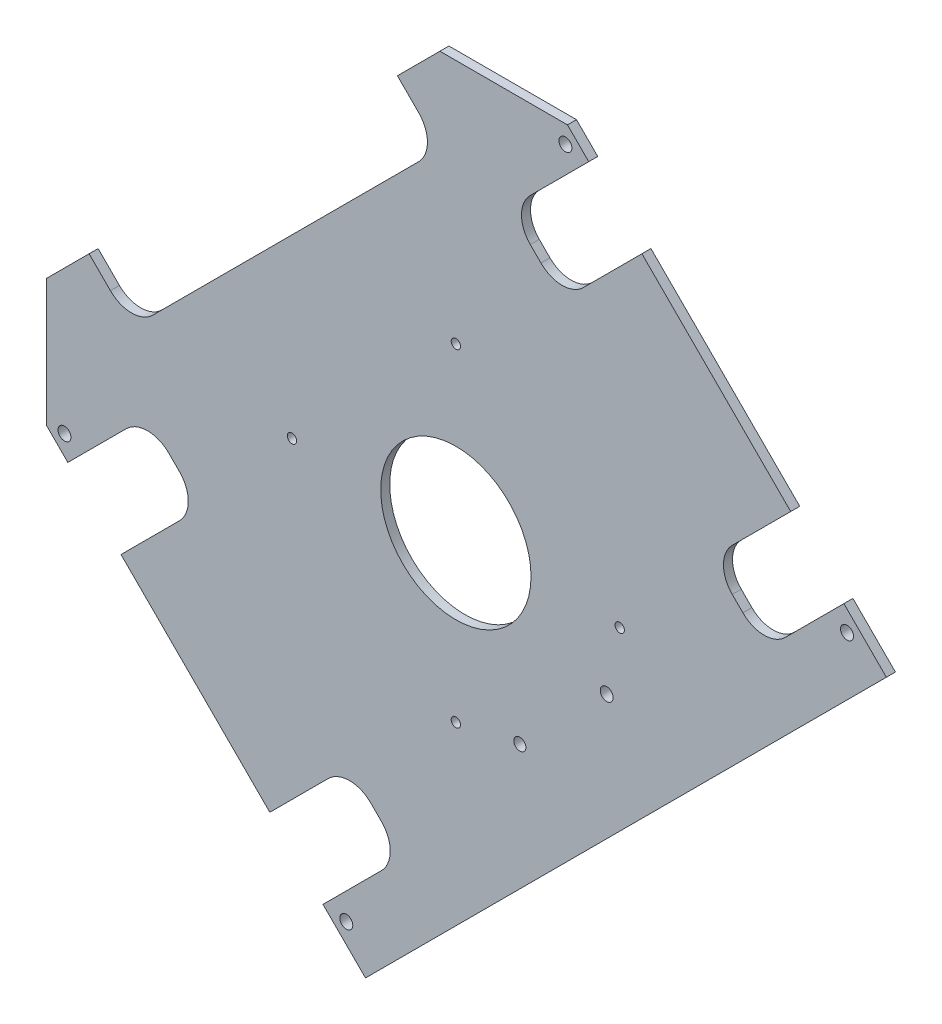
SolidWorks part; units mm, degrees
ref_plane "前视基准面" through (0, 0, 0) normal (0, 0, 1) x (1, 0, 0)
ref_plane "上视基准面" through (0, 0, 0) normal (0, 1, 0) x (1, 0, 0)
ref_plane "右视基准面" through (0, 0, 0) normal (1, 0, 0) x (0, 0, -1)
sketch "Sketch1" plane through (0, 0, 0) normal (0, 0, 1) x (1, 0, 0)
  line L16 (44.1941, 129.0469) -> (15.9098, 157.3312)
  line L17 (-110.8692, -62.3719) -> (-111.3693, -61.8718)
  line L18 (15.9098, 157.3312) -> (-19.4455, 121.9759)
  line L20 (61.1787, 112.0623) -> (111.3693, 61.8718)
  line L21 (-110.8692, -62.3719) -> (-61.8718, -111.3693)
  line L22 (143.1891, 30.052) -> (-30.052, -143.1891)
  line L23 (10.9602, -120.5617) -> (86.6206, -196.2221) construction
  line L24 (196.2221, -86.6206) -> (120.5617, -10.9602) construction
  line L25 (120.5617, -6.7176) -> (141.7749, 14.4956) construction
  line L26 (14.4956, 141.7749) -> (-6.7176, 120.5617) construction
  line L27 (61.1787, 112.0623) -> (61.8718, 111.3693)
  line L28 (44.1941, 129.0469) -> (17.6776, 102.5304)
  line L29 (61.8718, 111.3693) -> (35.3553, 84.8528)
  line L30 (17.6776, 102.5304) -> (35.3553, 84.8528)
  line L32 (111.3693, 61.8718) -> (84.8528, 35.3553)
  line L33 (129.0469, 44.1941) -> (102.5304, 17.6776)
  line L34 (84.8528, 35.3553) -> (102.5304, 17.6776)
  line L35 (56.5685, -56.5685) -> (-56.5685, 56.5685) construction
  line L36 (-35.3553, -84.8528) -> (-17.6776, -102.5304)
  line L37 (-44.1941, -129.0469) -> (-17.6776, -102.5304)
  line L38 (-61.8718, -111.3693) -> (-35.3553, -84.8528)
  line L40 (-102.5304, -17.6776) -> (-84.8528, -35.3553)
  line L41 (-111.3693, -61.8718) -> (-84.8528, -35.3553)
  line L42 (-129.0469, -44.1941) -> (-102.5304, -17.6776)
  line L44 (48.0832, 104.6517) -> (37.4766, 94.0451) construction
  line L45 (94.0451, 37.4766) -> (104.6517, 48.0832) construction
  line L46 (115.2584, 37.4766) -> (104.6517, 26.87) construction
  line L47 (102.5304, 24.7487) -> (98.9949, 28.2842) construction
  line L48 (28.2842, 98.9949) -> (24.7487, 102.5304) construction
  line L50 (-121.9759, 19.4455) -> (-107.8337, 5.3034)
  line L51 (-19.4455, 121.9759) -> (-5.3034, 107.8337)
  line L52 (-107.8337, 5.3034) -> (-5.3034, 107.8337)
  line L53 (-121.9759, 19.4455) -> (-157.3312, -15.9098)
  line L54 (129.0469, 44.1941) -> (143.1891, 30.052)
  line L55 (-129.0469, -44.1941) -> (-157.3312, -15.9098)
  line L56 (-44.1941, -129.0469) -> (-30.052, -143.1891)
  circle A0 centre (0, -54.5) radius 1.55 construction
  circle A1 centre (54.5, 0) radius 1.55 construction
  circle A2 centre (-54.5, 0) radius 1.55 construction
  circle A3 centre (0, 54.5) radius 1.55 construction
  circle A4 centre (0, -54.5) radius 1.55
  circle A5 centre (54.5, 0) radius 1.55
  circle A6 centre (-54.5, 0) radius 1.55
  circle A7 centre (0, 54.5) radius 1.55
  circle A8 centre (0, 0) radius 25
  circle A9 centre (50.1675, -21.2948) radius 2.15 construction
  circle A10 centre (21.2948, -50.1675) radius 2 construction
  circle A11 centre (21.2948, -50.1675) radius 2
  circle A12 centre (50.1675, -21.2948) radius 2.15
  point P53 (99.3484, 42.7799)
  dimension "D1" = 45
  dimension "D2" = 45
  dimension "D3" = 10
  dimension "D4" = 10
  dimension "D5" = 5
  dimension "D6" = 5
  dimension "D7" = 5
  dimension "D8" = 5
  dimension "D9" = 5
  dimension "D10" = 5
  dimension "D11" = 20
  dimension "D12" = 50
  dimension "D13" = 50
extrude "Extrude1" add sketch "Sketch1" along normal blind 3 contours L22 L35 A8 L52 L50 L53 L55 L42 L40 L41 L17 L21 L38 L36 L37 L56 A4 A6 A11 | L35 L22 L54 L33 L34 L32 L20 L29 L30 L28 L16 L18 L51 L52 A8 A12 A7 A5 region at (39.9762, 47.2202, 0) region at (-47.2126, -39.9774, 0)
fillet "Fillet1" radius 10 2 edges at (-5.3034, 107.8337, 1.5) (-107.8337, 5.3034, 1.5)
fillet "Fillet2" radius 10 8 edges at (35.3553, 84.8528, 1.5) (17.6776, 102.5304, 1.5) (84.8528, 35.3553, 1.5) (102.5304, 17.6776, 1.5) (-17.6776, -102.5304, 1.5) (-35.3553, -84.8528, 1.5) (-84.8528, -35.3553, 1.5) (-102.5304, -17.6776, 1.5)
chamfer "Chamfer1" distance 30 angle 45 2 edges at (-157.3312, -15.9098, 1.5) (15.9098, 157.3312, 1.5)
sketch "Sketch3" plane through (0, 0, 3) normal (0, 0, 1) x (1, 0, 0)
  circle A0 centre (130.0887, 36.3637) radius 2.15 construction
  circle A1 centre (36.4344, 130.1594) radius 2.15 construction
  circle A2 centre (-36.4344, -130.1594) radius 2.15 construction
  circle A3 centre (-130.1594, -36.4344) radius 2.15 construction
  circle A4 centre (130.0887, 36.3637) radius 2.15
  circle A5 centre (36.4344, 130.1594) radius 2.15
  circle A6 centre (-36.4344, -130.1594) radius 2.15
  circle A7 centre (-130.1594, -36.4344) radius 2.15
extrude "Cut-Extrude1" cut sketch "Sketch3" against normal blind 3
